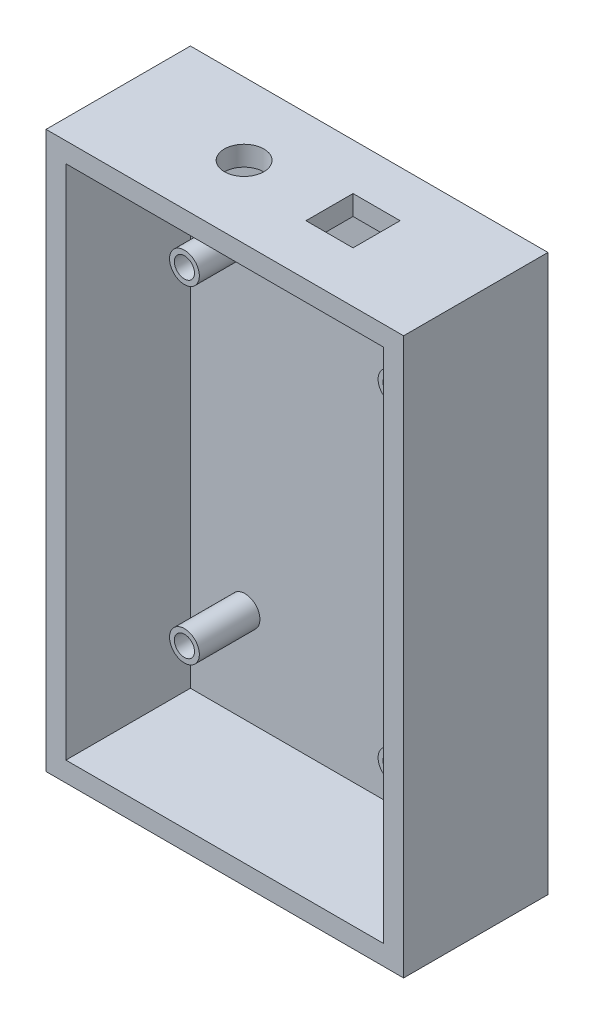
SolidWorks part; units mm, degrees
ref_plane "Front Plane" through (0, 0, 0) normal (0, 0, 1) x (1, 0, 0)
ref_plane "Top Plane" through (0, 0, 0) normal (0, 1, 0) x (1, 0, 0)
ref_plane "Right Plane" through (0, 0, 0) normal (1, 0, 0) x (0, 0, -1)
sketch "Sketch1" plane through (0, 0, 0) normal (0, 0, 1) x (1, 0, 0)
  line L0 (22.86, 35.56) -> (-22.86, -35.56) construction
  line L1 (-22.86, 35.56) -> (22.86, 35.56)
  line L2 (-22.86, 35.56) -> (-22.86, -35.56)
  line L3 (-22.86, -35.56) -> (22.86, -35.56)
  line L4 (22.86, 35.56) -> (22.86, -35.56)
  point P4 (0, 0)
  dimension "D1" = 71.12
  dimension "D2" = 45.72
extrude "Boss-Extrude1" add sketch "Sketch1" along normal mid plane 18.4568 contours L1 L4 L3 L2
shell "Shell3" thickness 2.54 removed face at (0, 0, 9.2284)
sketch "Sketch4" plane through (0, 0, -6.6884) normal (0, 0, 1) x (1, 0, 0)
  line L0 (-20.32, 0) -> (20.32, 0) construction
  line L1 (-20.32, 33.02) -> (-20.32, -33.02) construction
  line L2 (20.32, 33.02) -> (20.32, -33.02) construction
  circle A0 centre (-13.335, 20.955) radius 1.905
  circle A2 centre (13.335, 20.955) radius 1.905
  circle A3 centre (13.335, -20.955) radius 1.905
  circle A4 centre (-13.335, -20.955) radius 1.905
  dimension "D1" = 3.81
  dimension "D2" = 26.67
  dimension "D4" = 41.91
  dimension "D3" = 6.985
  dimension "D5" = 41.91
extrude "Boss-Extrude2" add sketch "Sketch4" along normal blind 7.7458
sketch "Sketch7" plane through (0, 0, 1.0575) normal (0, 0, 1) x (1, 0, 0)
  point P0 (-13.335, 20.955)
  point P1 (13.335, 20.955)
  point P3 (13.335, -20.955)
  point P5 (-13.335, -20.955)
  point P7 (0, 0)
hole_wizard "#5-40 Tapped Hole2" positions "Sketch10" profile "Sketch11" tap size "#5-40" standard "ANSI Inch"
sketch "Sketch10" plane through (0, 0, 1.0575) normal (0, 0, 1) x (1, 0, 0)
  point P0 (-13.335, 20.955)
  point P3 (13.335, 20.955)
  point P6 (-13.335, -20.955)
  point P9 (13.335, -20.955)
sketch "Sketch11" plane through (-13.335, 20.955, 1.0575) normal (1, 0, 0) x (0, -1, 0)
  line L0 (0, 0) -> (0, 5.6005)
  line L1 (0, 5.6005) -> (1.289, 4.826)
  line L2 (1.289, 4.826) -> (1.289, 0)
  line L5 (1.289, 0) -> (0, 0)
  line L10 (0, 5.6005) -> (-1.2891, 4.826) construction
  line L11 (0, -6.35) -> (0, 107.95) construction
  dimension "Tap Drill Dia." = 2.5781
  dimension "Tap Drill Depth" = 4.826
  dimension "Drill Angle" = 118
cosmetic thread "Hole Thread5" parameters "D1"=4.7625, "D2"=3.175
cosmetic thread "Hole Thread6" parameters "D1"=4.7625, "D2"=3.175
cosmetic thread "Hole Thread7" parameters "D1"=4.7625, "D2"=3.175
cosmetic thread "Hole Thread8" parameters "D1"=4.7625, "D2"=3.175
hole_wizard "#8 (0.199) Diameter Hole1" positions "Sketch12" profile "Sketch13" hole size "#8" standard "ANSI Inch" end condition up to next
sketch "Sketch12" plane through (0, 35.56, 0) normal (0, 1, 0) x (1, 0, 0)
  point P0 (-6.7619, 0)
  point P2 (-42.2856, -5.5596)
sketch "Sketch13" plane through (-6.7619, 35.56, 0) normal (1, 0, 0) x (0, 0, 1)
  line L0 (0, 0) -> (0, 2.54)
  line L1 (0, 2.54) -> (2.5273, 2.54)
  line L2 (2.5273, 2.54) -> (2.5273, 0)
  line L5 (2.5273, 0) -> (0, 0)
  line L11 (0, -6.35) -> (0, 107.95) construction
  dimension "Thru Hole Dia." = 5.0546
  dimension "Thru Hole Depth" = 2.54
sketch "Sketch14" plane through (0, 35.56, 0) normal (0, 1, 0) x (1, 0, 0)
  line L1 (3.874, 3.2905) -> (9.8938, 3.2905)
  line L2 (3.874, 3.2905) -> (3.874, -2.7293)
  line L3 (3.874, -2.7293) -> (9.8938, -2.7293)
  line L4 (9.8938, 3.2905) -> (9.8938, -2.7293)
  point P4 (0, 0)
  point P5 (0, 0)
  point P6 (0, 0)
  dimension "D1" = 6.0198
  dimension "D2" = 6.0198
extrude "Cut-Extrude1" cut sketch "Sketch14" against normal up to next
